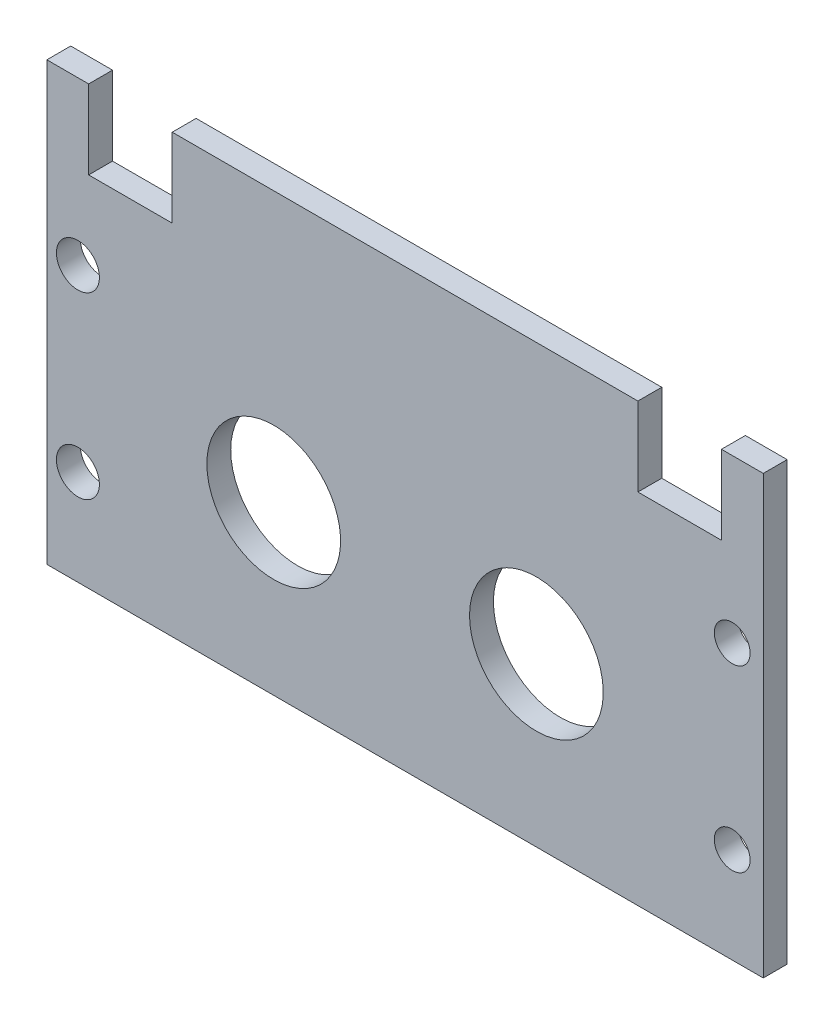
SolidWorks part; units mm, degrees
ref_plane "Ön Düzlem" through (0, 0, 0) normal (0, 0, 1) x (1, 0, 0)
ref_plane "Üst Düzlem" through (0, 0, 0) normal (0, 1, 0) x (1, 0, 0)
ref_plane "Sağ Düzlem" through (0, 0, 0) normal (1, 0, 0) x (0, 0, -1)
sketch "Çizim1" plane through (0, 0, 0) normal (0, 0, 1) x (1, 0, 0)
  line L1 (-150, -75) -> (150, -75)
  line L2 (-150, -75) -> (-150, 75)
  line L3 (-150, 75) -> (150, 75)
  line L4 (150, -75) -> (150, 75)
  line L5 (-150, -75) -> (150, 75) construction
  line L6 (-150, 75) -> (150, -75) construction
  point P0 (0, 0)
  dimension "D1" = 150
  dimension "D2" = 300
base flange "Taban-Flanş1" sketch "Çizim1" thickness 10 reverse thickness direction no parameters "D1"=0.7366
sketch "Çizim2" plane through (0, 0, -10) normal (0, 0, -1) x (-1, 0, 0)
  line L0 (-55, -5) -> (55, -5) construction
  line L1 (55, -5) -> (-55, -5) construction
  line L2 (150, -75) -> (-150, -75) construction
  circle A0 centre (-55, -5) radius 28
  circle A1 centre (55, -5) radius 28
  point P2 (0, -5)
  dimension "D1" = 56
  dimension "D2" = 110
  dimension "D3" = 70
extrude "Kes-Ekstrüzyon1" cut sketch "Çizim2" against normal blind 10 normal cut yes
sketch "Çizim3" plane through (0, 0, -10) normal (0, 0, -1) x (-1, 0, 0)
  line L0 (-150, -75) -> (-150, 75) construction
  line L1 (150, -75) -> (-150, -75) construction
  line L2 (-150, 75) -> (150, 75) construction
  circle A0 centre (-137, -35) radius 7.5
  circle A1 centre (-137, 40) radius 7.5
  dimension "D2" = 15
  dimension "D1" = 13
  dimension "D3" = 40
  dimension "D4" = 35
extrude "Kes-Ekstrüzyon2" cut sketch "Çizim3" against normal blind 10 normal cut yes
sketch "Çizim4" plane through (0, 0, -10) normal (0, 0, -1) x (-1, 0, 0)
  line L1 (-150, 75) -> (150, 75) construction
  line L2 (150, -75) -> (-150, -75) construction
  line L3 (150, 75) -> (150, -75) construction
  circle A0 centre (137, -35) radius 7.5
  circle A1 centre (137, 40) radius 7.5
  point P6 (0, 0)
  point P7 (0, 0)
  point P10 (141.7985, 66.6988)
  dimension "D1" = 15
  dimension "D2" = 75
  dimension "D4" = 35
  dimension "D5" = 40
  dimension "D6" = 13
extrude "Kes-Ekstrüzyon3" cut sketch "Çizim4" against normal blind 10 normal cut yes
sketch "Çizim5" plane through (0, 0, -10) normal (0, 0, -1) x (-1, 0, 0)
  circle A0 centre (137, -35) radius 9
  circle A1 centre (137, 40) radius 9
  dimension "D1" = 18
  dimension "D2" = 18
  dimension "D3" = 75
extrude "Kes-Ekstrüzyon4" cut sketch "Çizim5" against normal through all normal cut yes
sketch "Çizim8" plane through (0, 0, -10) normal (0, 0, -1) x (-1, 0, 0)
  line L0 (-150, 75) -> (150, 75) construction
  line L1 (150, 75) -> (132.5, 75)
  line L2 (150, 75) -> (150, 108)
  line L3 (150, 108) -> (132.5, 108)
  line L4 (132.5, 75) -> (132.5, 108)
  line L5 (97.5, 75) -> (-97.5, 75)
  line L6 (97.5, 75) -> (97.5, 108)
  line L7 (97.5, 108) -> (-97.5, 108)
  line L8 (-97.5, 75) -> (-97.5, 108)
  line L10 (-132.5, 75) -> (-150, 75)
  line L11 (-132.5, 75) -> (-132.5, 108)
  line L12 (-132.5, 108) -> (-150, 108)
  line L13 (-150, 75) -> (-150, 108)
  dimension "D1" = 33
base flange "Sekme1" sketch "Çizim8" thickness 10 reverse thickness direction no parameters "D1"=0.7366
sketch "Büküm-Çizgileri1" [suppressed] plane through (0, 0, 0) normal (0, 1, 0) x (1, 0, 0)
sketch "Sınırlandırma-Kutusu1" [suppressed] plane through (0, 0, 0) normal (0, 1, 0) x (1, 0, 0)
sheet metal parameters "Sac-Levha1" thickness 10 parameters "D1"=0.7366
flat pattern "Düz-Çoğaltma1" [suppressed]
sketch "Büküm-Çizgileri2" plane through (0, 0, 0) normal (0, 1, 0) x (1, 0, 0)
sketch3d "Sınırlandırma-Kutusu2" [suppressed]
  line L0 (165, -75, 0) -> (-165, -75, 0) construction
  line L1 (165, 75, 0) -> (-165, 75, 0) construction
  line L2 (165, -75, 0) -> (165, 75, 0) construction
  line L3 (-165, -75, 0) -> (-165, 75, 0) construction
sheet metal parameters "Sac-Levha2" thickness 10 parameters "D1"=0.7366
flat pattern "Düz-Çoğaltma1"
sketch "Büküm-Çizgileri2" plane through (0, 0, 0) normal (0, 1, 0) x (1, 0, 0)
sketch3d "Sınırlandırma-Kutusu2" [suppressed]
  line L0 (-150, -75, 0) -> (150, -75, 0) construction
  line L1 (-150, 75, 0) -> (150, 75, 0) construction
  line L2 (-150, -75, 0) -> (-150, 75, 0) construction
  line L3 (150, -75, 0) -> (150, 75, 0) construction
sheet metal parameters "Sac-Levha3" thickness 10 parameters "D1"=0.7366
flat pattern "Düz-Çoğaltma1"
sketch "Büküm-Çizgileri2" plane through (0, 0, 0) normal (0, 1, 0) x (1, 0, 0)
sketch3d "Sınırlandırma-Kutusu2" [suppressed]
  line L0 (-150, -75, 0) -> (150, -75, 0) construction
  line L1 (-150, 75, 0) -> (150, 75, 0) construction
  line L2 (-150, -75, 0) -> (-150, 75, 0) construction
  line L3 (150, -75, 0) -> (150, 75, 0) construction
sheet metal parameters "Sac-Levha4" thickness 10 parameters "D1"=0.7366
flat pattern "Düz-Çoğaltma1"
sketch "Büküm-Çizgileri2" plane through (0, 0, 0) normal (0, 1, 0) x (1, 0, 0)
sketch3d "Sınırlandırma-Kutusu2" [suppressed]
  line L0 (-150, -75, 0) -> (150, -75, 0) construction
  line L1 (-150, 75, 0) -> (150, 75, 0) construction
  line L2 (-150, -75, 0) -> (-150, 75, 0) construction
  line L3 (150, -75, 0) -> (150, 75, 0) construction
sheet metal parameters "Sac-Levha5" thickness 10 parameters "D1"=0.7366
flat pattern "Düz-Çoğaltma1"
sketch "Büküm-Çizgileri2" plane through (0, 0, 0) normal (0, 1, 0) x (1, 0, 0)
sketch3d "Sınırlandırma-Kutusu2" [suppressed]
  line L0 (-150, -75, 0) -> (150, -75, 0) construction
  line L1 (-150, 75, 0) -> (150, 75, 0) construction
  line L2 (-150, -75, 0) -> (-150, 75, 0) construction
  line L3 (150, -75, 0) -> (150, 75, 0) construction
sheet metal parameters "Sac-Levha6" thickness 10 parameters "D1"=0.7366
flat pattern "Düz-Çoğaltma6"
sketch "Büküm-Çizgileri3" plane through (0, 0, 0) normal (0, 1, 0) x (1, 0, 0)
sketch3d "Sınırlandırma-Kutusu3" [suppressed]
  line L0 (-150, -75, 0) -> (150, -75, 0) construction
  line L1 (-150, 108, 0) -> (150, 108, 0) construction
  line L2 (-150, -75, 0) -> (-150, 108, 0) construction
  line L3 (150, -75, 0) -> (150, 108, 0) construction
